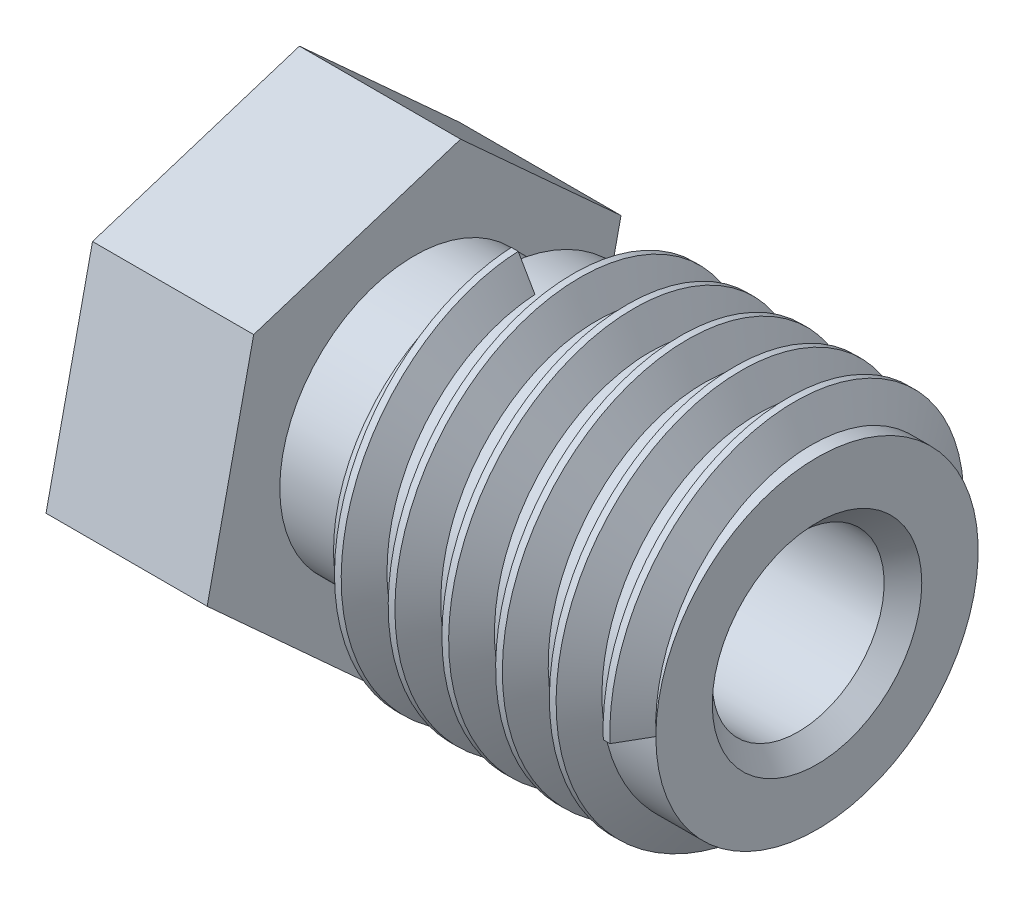
SolidWorks part; units mm, degrees
material "Brass"
ref_plane "Front Plane" through (0, 0, 0) normal (0, 0, 1) x (1, 0, 0)
ref_plane "Top Plane" through (0, 0, 0) normal (0, 1, 0) x (1, 0, 0)
ref_plane "Right Plane" through (0, 0, 0) normal (1, 0, 0) x (0, 0, -1)
sketch "Sketch1" plane through (0, 0, 0) normal (0, 0, 1) x (1, 0, 0)
  line L0 (2.6588, 0.7878) -> (2.6588, 1.8378)
  line L1 (2.6588, 1.8378) -> (-3.3412, 1.8378)
  line L2 (-3.3412, 1.8378) -> (-3.3412, 1.3378)
  line L3 (-3.3412, 1.3378) -> (-4.8412, 1.3378)
  line L4 (-4.8412, 1.3378) -> (-4.8412, 2.3378)
  line L5 (-4.8412, 2.3378) -> (-7.8412, 2.3378)
  line L6 (-7.8412, 2.3378) -> (-7.8412, 0.6678)
  line L7 (-7.8412, 0.6678) -> (-9.8412, -0.4869)
  line L8 (-9.8412, -0.4869) -> (-9.8412, -0.9869)
  line L9 (-9.8412, -0.9869) -> (-9.3112, -0.9869)
  line L10 (-9.3112, -0.9869) -> (-6.8435, 0.4378)
  line L11 (-6.8435, 0.4378) -> (2.3088, 0.4378)
  line L12 (2.3088, 0.4378) -> (2.6588, 0.7878)
  line L13 (-10.0755, -1.1622) -> (4.1156, -1.1622) construction
  dimension "D1" = 6
  dimension "D2" = 1.5
  dimension "D3" = 3
  dimension "D4" = 135
  dimension "D5" = 12.5
  dimension "D6" = 0.53
  dimension "D7" = 0.5
  dimension "D8" = 1.6
  dimension "D9" = 3.5
  dimension "D10" = 3
  dimension "D11" = 2.5
  dimension "D12" = 1.95
  dimension "D13" = 120
  dimension "D14" = 1.83
revolve "Revolve1" add sketch "Sketch1" angle 360 about L13
sketch "Sketch2" plane through (-4.8412, 0, 0) normal (1, 0, 0) x (0, 0, -1)
  line L1 (3.8516, 0.0618) -> (0.8658, 2.7854)
  line L2 (0.8658, 2.7854) -> (-2.9859, 1.5613)
  line L3 (-2.9859, 1.5613) -> (-3.8516, -2.3863)
  line L4 (-3.8516, -2.3863) -> (-0.8658, -5.1099)
  line L5 (-0.8658, -5.1099) -> (2.9859, -3.8858)
  line L6 (2.9859, -3.8858) -> (3.8516, 0.0618)
  circle A0 centre (0, -1.1622) radius 3.5 construction
  dimension "D1" = 7
extrude "Boss-Extrude1" add sketch "Sketch2" against normal blind 3
thread "Thread1" pitch 1 start angle 0, offset 0, length 0, pitch 1, diameter 6
ref_plane "Plane1" through (2.6588, -1.1622, 3) normal (0, -1, 0) x (0, 0, 1)
sketch "Thread Profile1" plane through (2.6588, -1.1622, 3) normal (0, -1, 0) x (0, 0, 1)
  line L0 (0, 0) -> (0, 1) construction
  line L1 (0, 0) -> (0.5413, 0.3125)
  line L2 (0.5413, 0.3125) -> (0.5413, 0.4375)
  line L3 (0.5413, 0.4375) -> (0, 0.75)
  line L4 (0.5413, 0.375) -> (0, 0.375) construction
  line L11 (0, 0) -> (0, 0.75)
  point P2 (0, 0)
  dimension "Pitch" = 1
  dimension "Profile_Angle" = 60
  dimension "Profile_Land" = 0.125
  dimension "Profile_Height" = 0.5413
